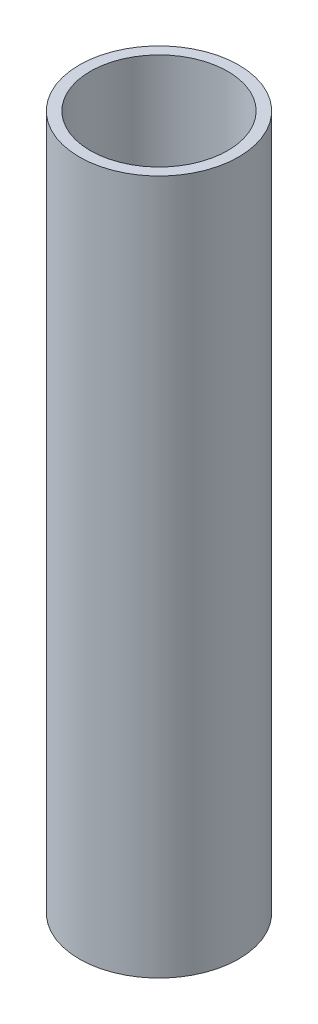
SolidWorks part; units mm, degrees
material "Epoxy, Unfilled"
ref_plane "Front Plane" through (0, 0, 0) normal (0, 0, 1) x (1, 0, 0)
ref_plane "Top Plane" through (0, 0, 0) normal (0, 1, 0) x (1, 0, 0)
ref_plane "Right Plane" through (0, 0, 0) normal (1, 0, 0) x (0, 0, -1)
sketch "Sketch2" plane through (0, 0, 0) normal (0, 1, 0) x (1, 0, 0)
  circle A0 centre (0, 0) radius 58.293
  circle A1 centre (0, 0) radius 50.2539
extrude "Boss-Extrude1" add sketch "Sketch2" along normal blind 508
